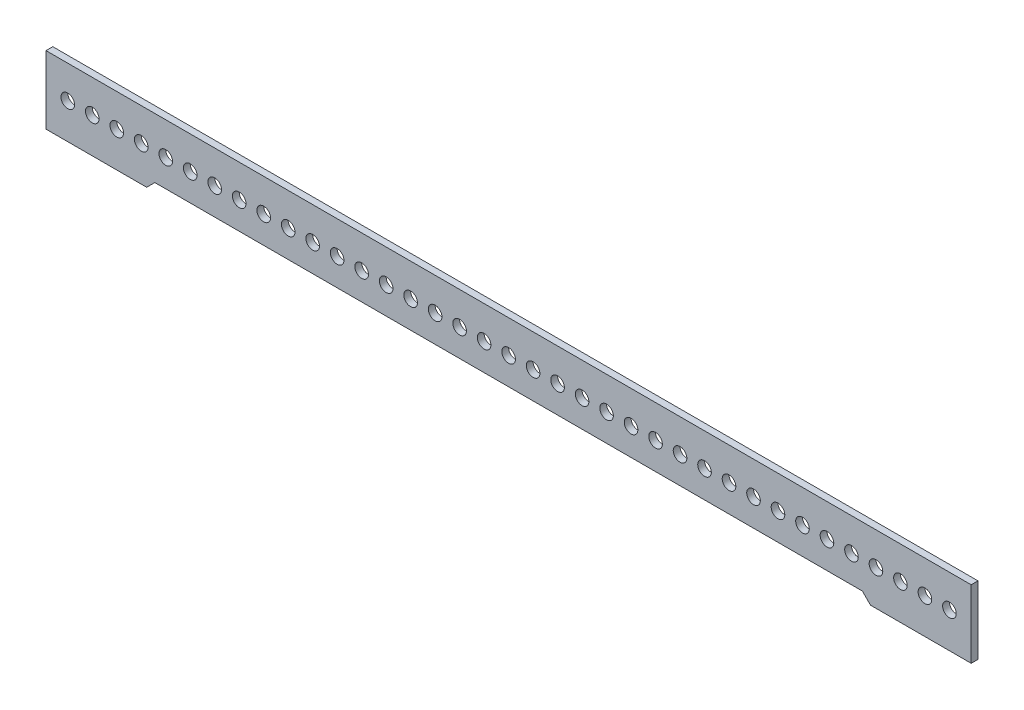
SolidWorks part; units mm, degrees
ref_plane "Front Plane" through (0, 0, 0) normal (0, 0, 1) x (1, 0, 0)
ref_plane "Top Plane" through (0, 0, 0) normal (0, 1, 0) x (1, 0, 0)
ref_plane "Right Plane" through (0, 0, 0) normal (1, 0, 0) x (0, 0, -1)
sketch "Sketch1" plane through (0, 0, 0) normal (0, 0, 1) x (1, 0, 0)
  line L0 (-215.9, 0) -> (215.9, 0)
  line L2 (215.9, -31.75) -> (168.91, -31.75)
  line L3 (168.91, -31.75) -> (165.1, -27.94)
  line L4 (165.1, -27.94) -> (-165.1, -27.94)
  line L5 (-165.1, -27.94) -> (-168.91, -31.75)
  line L6 (-168.91, -31.75) -> (-215.9, -31.75)
  line L8 (-215.9, -31.75) -> (-215.9, 0)
  line L9 (215.9, 0) -> (215.9, -31.75)
  dimension "D1" = 431.8
  dimension "D2" = 31.75
  dimension "D3" = 330.2
  dimension "D4" = 3.81
extrude "Boss-Extrude1" add sketch "Sketch1" along normal blind 3.175
sketch "Sketch3" plane through (0, 0, 3.175) normal (0, 0, 1) x (1, 0, 0)
  line L0 (215.9, 0) -> (-215.9, 0) construction
  line L1 (-205.74, -15.24) -> (-215.9, -15.24) construction
  line L2 (-205.74, -15.24) -> (-194.31, -15.24) construction
  line L4 (-215.9, 0) -> (-215.9, -31.75) construction
  line L5 (205.74, -15.24) -> (215.9, -15.24) construction
  line L6 (215.9, -31.75) -> (215.9, 0) construction
  circle A0 centre (-205.74, -15.24) radius 3.175
  circle A1 centre (-194.31, -15.24) radius 3.175
  circle A2 centre (-182.88, -15.24) radius 3.175
  circle A3 centre (-171.45, -15.24) radius 3.175
  circle A4 centre (-160.02, -15.24) radius 3.175
  circle A5 centre (-148.59, -15.24) radius 3.175
  circle A6 centre (-137.16, -15.24) radius 3.175
  circle A7 centre (-125.73, -15.24) radius 3.175
  circle A8 centre (-114.3, -15.24) radius 3.175
  circle A9 centre (-102.87, -15.24) radius 3.175
  circle A10 centre (-91.44, -15.24) radius 3.175
  circle A11 centre (-80.01, -15.24) radius 3.175
  circle A12 centre (-68.58, -15.24) radius 3.175
  circle A13 centre (-57.15, -15.24) radius 3.175
  circle A14 centre (-45.72, -15.24) radius 3.175
  circle A15 centre (-34.29, -15.24) radius 3.175
  circle A16 centre (-22.86, -15.24) radius 3.175
  circle A17 centre (-11.43, -15.24) radius 3.175
  circle A18 centre (0, -15.24) radius 3.175
  circle A19 centre (11.43, -15.24) radius 3.175
  circle A20 centre (22.86, -15.24) radius 3.175
  circle A21 centre (34.29, -15.24) radius 3.175
  circle A22 centre (45.72, -15.24) radius 3.175
  circle A23 centre (57.15, -15.24) radius 3.175
  circle A24 centre (68.58, -15.24) radius 3.175
  circle A25 centre (80.01, -15.24) radius 3.175
  circle A26 centre (91.44, -15.24) radius 3.175
  circle A27 centre (102.87, -15.24) radius 3.175
  circle A28 centre (114.3, -15.24) radius 3.175
  circle A29 centre (125.73, -15.24) radius 3.175
  circle A30 centre (137.16, -15.24) radius 3.175
  circle A31 centre (148.59, -15.24) radius 3.175
  circle A32 centre (160.02, -15.24) radius 3.175
  circle A33 centre (171.45, -15.24) radius 3.175
  circle A34 centre (182.88, -15.24) radius 3.175
  circle A35 centre (194.31, -15.24) radius 3.175
  circle A36 centre (205.74, -15.24) radius 3.175
  dimension "D1" = 6.35
  dimension "D2" = 15.24
  dimension "D5" = 11.43
  dimension "D4" = 37
extrude "Cut-Extrude2" cut sketch "Sketch3" against normal through all
